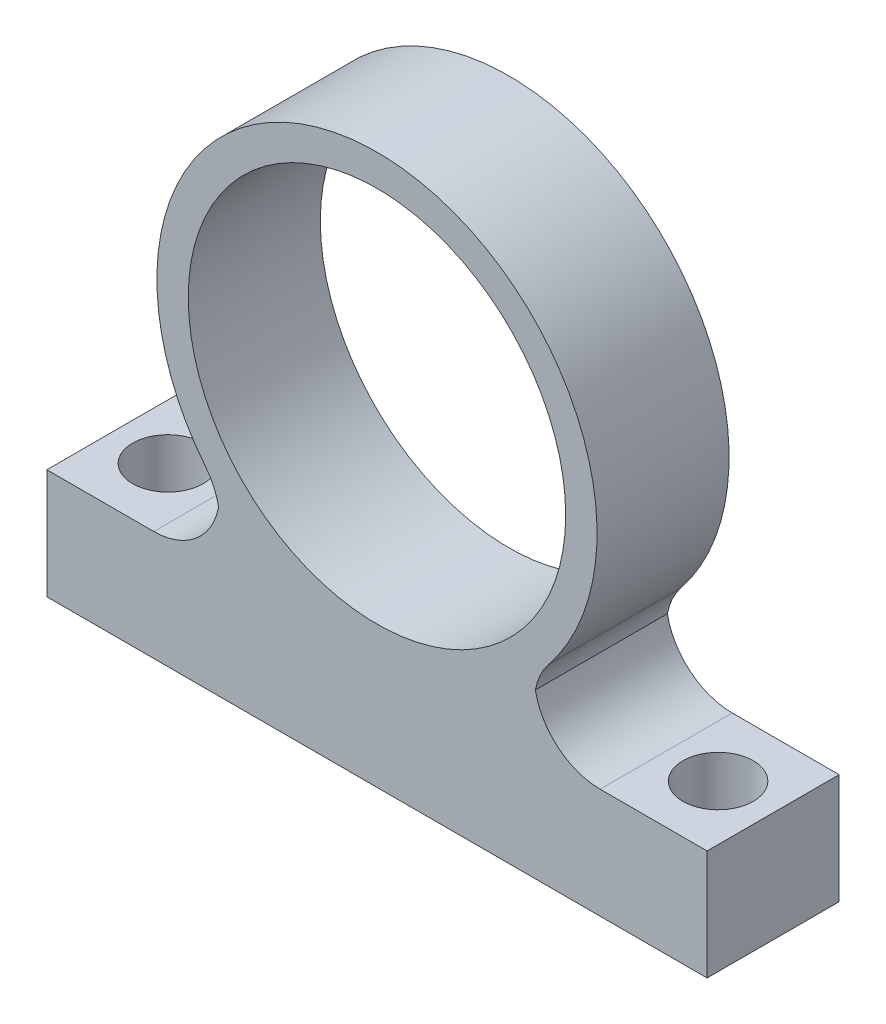
SolidWorks part; units mm, degrees
ref_plane "Front Plane" through (0, 0, 0) normal (0, 0, 1) x (1, 0, 0)
ref_plane "Top Plane" through (0, 0, 0) normal (0, 1, 0) x (1, 0, 0)
ref_plane "Right Plane" through (0, 0, 0) normal (1, 0, 0) x (0, 0, -1)
sketch "Çizim1" plane through (0, 0, 0) normal (0, 0, 1) x (1, 0, 0)
  line L0 (-7.1414, 2.5) -> (-7.1414, 5.5)
  line L1 (-15, -2.5) -> (15, -2.5)
  line L2 (-15, -2.5) -> (-15, 2.5)
  line L3 (-15, 2.5) -> (15, 2.5)
  line L4 (15, -2.5) -> (15, 2.5)
  line L5 (-15, -2.5) -> (15, 2.5) construction
  line L6 (-15, 2.5) -> (15, -2.5) construction
  line L7 (7.1414, 2.5) -> (7.1414, 5.5)
  circle A0 centre (0, 12.5) radius 10
  circle A1 centre (0, 12.5) radius 8.575
  point P0 (0, 0)
  dimension "D7" = 20
  dimension "D8" = 10
  dimension "D9" = 15
  dimension "D3" = 17.15
  dimension "D1" = 30
  dimension "D2" = 5
  dimension "D4" = 3
  dimension "D5" = 3
extrude "Yükseklik-Ekstrüzyon1" add sketch "Çizim1" along normal blind 6 contours A0 A1 | A0 L3 L7 | A0 L0 L3 | L1 L4 L3 L2 region at (0, 0, 0) region at (-5.4141, 3.371, 0) region at (-3.6737, 21.496, 0) region at (5.4141, 3.371, 0)
fillet "Radyus1" radius 3 4 edges at (-7.1414, 2.5, 3) (-7.1414, 5.5, 3) (7.1414, 5.5, 3) (7.1414, 2.5, 3)
sketch "Çizim2" plane through (0, 2.5, 0) normal (0, 1, 0) x (1, 0, 0)
  line L0 (-15, 0) -> (-10.1414, 0) construction
  line L1 (-15, -6) -> (-15, 0) construction
  circle A0 centre (-12.5, -3) radius 1.6
  dimension "D1" = 3.2
  dimension "D2" = 3
  dimension "D3" = 2.5
sketch "Çizim3" plane through (0, 2.5, 0) normal (0, 1, 0) x (1, 0, 0)
  line L0 (10.1414, 0) -> (15, 0) construction
  line L1 (15, -6) -> (15, 0) construction
  circle A0 centre (12.5, -3) radius 1.6
  dimension "D1" = 3.2
  dimension "D2" = 3
  dimension "D3" = 2.5
extrude "Kes-Ekstrüzyon1" cut sketch "Çizim3" against normal blind 6
extrude "Kes-Ekstrüzyon2" cut sketch "Çizim2" against normal blind 6
